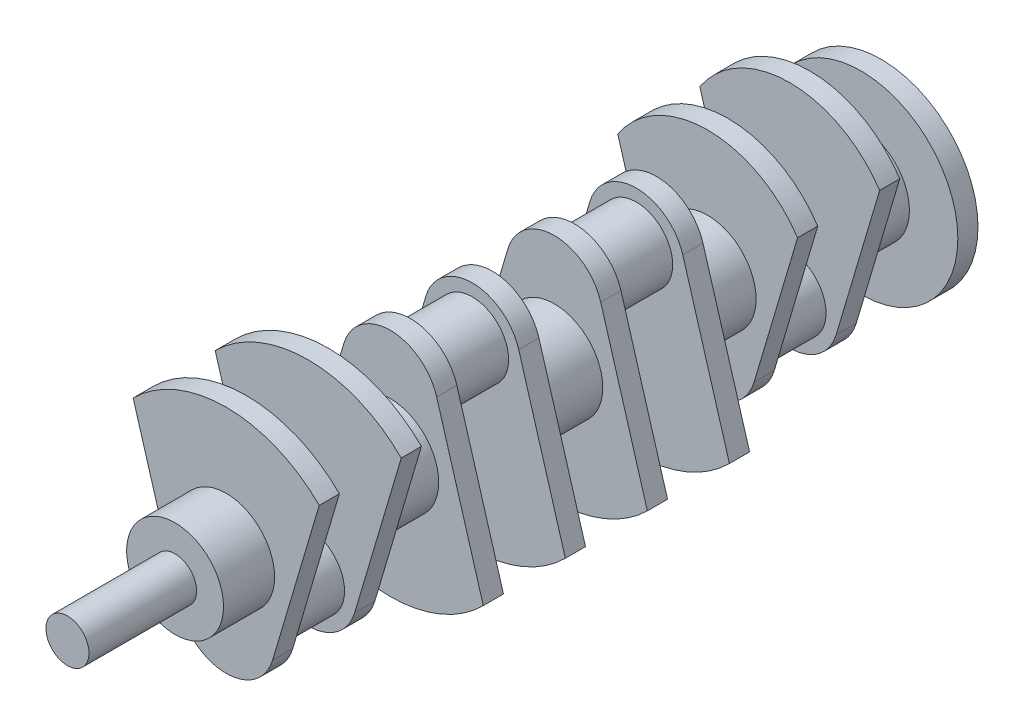
SolidWorks part; units mm, degrees
ref_plane "Plano frontal" through (0, 0, 0) normal (0, 0, 1) x (1, 0, 0)
ref_plane "Plano superior" through (0, 0, 0) normal (0, 1, 0) x (1, 0, 0)
ref_plane "Plano direito" through (0, 0, 0) normal (1, 0, 0) x (0, 0, -1)
sketch "Esboço1" plane through (0, 0, 0) normal (0, 0, 1) x (1, 0, 0)
  circle A0 centre (0, 0) radius 72
  circle A1 centre (0, 0) radius 36
  dimension "D1" = 144
  dimension "D2" = 72
extrude "Ressalto-extrusão1" add sketch "Esboço1" along normal blind 15 contours A1 | A0 A1 region at (-69.9635, 0, 0) region at (0, 0, 0)
extrude "Ressalto-extrusão2" add sketch "Esboço1<3>" along normal blind 53 contours A1 region at (0, 0, 0)
sketch "Esboço1<3>" plane through (0, 0, 0) normal (0, 0, 1) x (1, 0, 0) same geometry as "Esboço1"
sketch "Esboço2" plane through (0, 0, 53) normal (0, 0, 1) x (1, 0, 0)
  line L0 (-117.0522, 0) -> (117.0522, 0) construction
  line L1 (0, 45.2622) -> (0, -45.2622) construction
  line L2 (34.5175, -54.2246) -> (66.844, 54.9078)
  line L3 (-34.5175, -54.2246) -> (-66.844, 54.9078)
  circle A1 centre (0, -44) radius 36
  circle A2 centre (0, 0) radius 36 construction
  arc A3 (-66.844, 54.9078) -> (66.844, 54.9078) centre (0, 10.9546) cw
  point P4 (0, 0)
  point P8 (0, 0)
  circle M3 centre (0, 0) radius 36
  dimension "D1" = 72
  dimension "D2" = 44
  dimension "D4" = 80
  dimension "D3" = 33
extrude "Ressalto-extrusão3" add sketch "Esboço2" along normal blind 15 contours A3 L3 A1 L2 M3 | A1 M3 | A1 M3 | A1 M3 region at (0, 42.7995, 53) region at (0, -52.2821, 53) region at (0, 8.2821, 53) region at (0, -22, 53)
sketch "Esboço3" plane through (0, 0, 68) normal (0, 0, 1) x (1, 0, 0)
  line L0 (-140.7419, 0) -> (140.7419, 0) construction
  line L1 (0, 38.6491) -> (0, -38.6491) construction
  circle A0 centre (0, -44) radius 27
  point P4 (0, 0)
  point P8 (0, 0)
  dimension "D1" = 44
  dimension "D2" = 54
extrude "Ressalto-extrusão4" add sketch "Esboço3" along normal blind 46
sketch "Esboço4" plane through (0, 0, 114) normal (0, 0, 1) x (1, 0, 0)
  line L0 (-132.2013, 0) -> (132.2013, 0) construction
  line L1 (0, 92.3837) -> (0, -92.3837) construction
  line L2 (-34.5175, -54.2246) -> (-66.8433, 54.9054)
  line L3 (34.5175, -54.2246) -> (66.8433, 54.9054)
  circle A0 centre (0, -44) radius 36
  arc A1 (-66.8433, 54.9054) -> (66.8433, 54.9054) centre (0, 10.9512) cw
  point P4 (0, 0)
  point P8 (0, 0)
  circle M3 centre (0, -44) radius 27
  dimension "D1" = 72
  dimension "D3" = 80
  dimension "D4" = 44
  dimension "D2" = 33
  dimension "D5" = 109.13
extrude "Ressalto-extrusão5" add sketch "Esboço4" along normal blind 15 contours A1 L2 A0 L3 | A0 M3 | M3 region at (0, 34.0654, 114) region at (-5.0196, -9.3802, 114) region at (0, -44, 114)
sketch "Esboço5" plane through (0, 0, 129) normal (0, 0, 1) x (1, 0, 0)
  line L0 (-127.5752, 0) -> (127.5752, 0) construction
  line L1 (0, 51.1041) -> (0, -51.1041) construction
  circle A0 centre (0, 0) radius 36
  point P4 (0, 0)
  point P8 (0, 0)
  dimension "D1" = 72
extrude "Ressalto-extrusão6" add sketch "Esboço5" along normal blind 38
sketch "Esboço6" plane through (0, 0, 167) normal (0, 0, 1) x (1, 0, 0)
  line L0 (0, 135.2261) -> (0, -162.3966) construction
  line L1 (-34.5175, 54.2246) -> (-69.1758, -62.7797)
  line L2 (34.5175, 54.2246) -> (69.1758, -62.7797)
  circle A0 centre (0, 44) radius 36
  circle A1 centre (0, 0) radius 36 construction
  arc A2 (-69.1758, -62.7797) -> (69.1758, -62.7797) centre (0, 6.396) ccw
  circle M1 centre (0, 0) radius 36
  dimension "D1" = 72
  dimension "D2" = 44
  dimension "D3" = 33
extrude "Ressalto-extrusão7" add sketch "Esboço6" along normal blind 15 contours L0 A2 L2 A0 M1 | L0 A0 L1 A2 M1 | A0 L0 M1 | L0 A0 M1 | A0 L0 M1 | L0 A0 M1 | L0 A0 M1 | L0 A0 M1 region at (16.8783, 52.2821, 167) region at (-16.8783, 52.2821, 167) region at (11.0302, 22, 167) region at (-11.0302, 22, 167) region at (33.331, -44.1593, 167) region at (-33.331, -44.1593, 167) region at (16.8783, -8.2821, 167) region at (-16.8783, -8.2821, 167)
sketch "Esboço7" plane through (0, 0, 182) normal (0, 0, 1) x (1, 0, 0)
  line L0 (0, 141.8355) -> (0, -146.754) construction
  circle A0 centre (0, 44) radius 27
  dimension "D1" = 54
  dimension "D2" = 44
extrude "Ressalto-extrusão8" add sketch "Esboço7" along normal blind 46
sketch "Esboço8" plane through (0, 0, 228) normal (0, 0, 1) x (1, 0, 0)
  line L0 (0, 154.0633) -> (0, -174.2233) construction
  line L1 (34.5175, 54.2246) -> (69.1745, -62.7754)
  line L2 (-34.5175, 54.2246) -> (-69.1745, -62.7754)
  circle A0 centre (0, 44) radius 36
  arc A1 (-69.1745, -62.7754) -> (69.1745, -62.7754) centre (0, 7.9072) ccw
  circle M4 centre (0, 44) radius 27
  dimension "D1" = 72
  dimension "D2" = 33
  dimension "D3" = 117
extrude "Ressalto-extrusão9" add sketch "Esboço8" along normal blind 15 contours A0 L0 A1 L1 | L0 A0 L2 A1 | L0 M4 | A0 L0 M4 | L0 A0 M4 | L0 M4 region at (21.058, 72.2001, 228) region at (-0.805, 75.5, 228) region at (11.4592, 44, 228) region at (-11.4592, 44, 228) region at (29.3155, -35.2045, 228) region at (-29.3155, -35.2045, 228)
sketch "Esboço11" plane through (0, 0, 243) normal (0, 0, 1) x (1, 0, 0)
  circle A0 centre (0, 0) radius 36
  dimension "D1" = 72
extrude "Ressalto-extrusão10" add sketch "Esboço11" along normal blind 46
sketch "Esboço12" plane through (0, 0, 289) normal (0, 0, 1) x (1, 0, 0)
  line L0 (0, 133.4771) -> (0, -162.5348) construction
  line L1 (34.5175, 54.2246) -> (69.1745, -62.7754)
  line L2 (-34.5175, 54.2246) -> (-69.1745, -62.7754)
  circle A0 centre (0, 44) radius 36
  arc A1 (-69.1745, -62.7754) -> (69.1745, -62.7754) centre (0, 6.399) ccw
  circle M1 centre (0, 0) radius 36
  dimension "D1" = 72
  dimension "D2" = 44
  dimension "D3" = 33
  dimension "D4" = 117
extrude "Ressalto-extrusão11" add sketch "Esboço12" along normal blind 15 contours L0 A1 L1 A0 M1 | L0 A0 L2 A1 M1 | L0 A0 M1 | L0 A0 M1 | L0 A0 M1 | L0 A0 M1 | A0 L0 M1 | A0 L0 M1 region at (16.8783, 52.2821, 289) region at (-16.8783, 52.2821, 289) region at (11.0302, 22, 289) region at (-11.0302, 22, 289) region at (33.3308, -44.1564, 289) region at (-33.3308, -44.1564, 289) region at (16.8783, -8.2821, 289) region at (-16.8783, -8.2821, 289)
sketch "Esboço13" plane through (0, 0, 304) normal (0, 0, 1) x (1, 0, 0)
  line L0 (0, 139.499) -> (0, -151.7865) construction
  circle A0 centre (0, 44) radius 27
  dimension "D1" = 54
  dimension "D2" = 44
extrude "Ressalto-extrusão12" add sketch "Esboço13" along normal blind 46
sketch "Esboço15" plane through (0, 0, 350) normal (0, 0, 1) x (1, 0, 0)
  line L0 (0, 127.6901) -> (0, -152.4425) construction
  line L1 (-34.5175, 54.2246) -> (-69.1745, -62.7754)
  line L2 (34.5175, 54.2246) -> (69.1745, -62.7754)
  circle A2 centre (0, 44) radius 36
  arc A3 (-69.1745, -62.7754) -> (69.1745, -62.7754) centre (0, 6.0031) ccw
  circle M1 centre (0, 44) radius 27
  dimension "D1" = 72
  dimension "D2" = 44
  dimension "D3" = 33
  dimension "D4" = 117
extrude "Ressalto-extrusão13" add sketch "Esboço15" along normal blind 15 contours L0 A2 L1 A3 | A2 L0 A3 L2 | L0 M1 | L0 M1 | A2 L0 M1 | A2 region at (21.058, 72.2001, 350) region at (11.4592, 44, 350) region at (-11.4592, 44, 350) region at (29.3077, -35.4366, 350) region at (-29.3077, -35.4366, 350)
sketch "Esboço16" plane through (0, 0, 365) normal (0, 0, 1) x (1, 0, 0)
  line L0 (0, 141.498) -> (0, -185.4139) construction
  circle A0 centre (0, 0) radius 36
  dimension "D1" = 72
extrude "Ressalto-extrusão14" add sketch "Esboço16" along normal blind 46
sketch "Esboço18" plane through (0, 0, 411) normal (0, 0, 1) x (1, 0, 0)
  line L0 (0, 175.3672) -> (0, -173.498) construction
  line L1 (-34.5175, -54.2246) -> (-69.1745, 62.7754)
  line L2 (34.5175, -54.2246) -> (69.1745, 62.7754)
  circle A0 centre (0, -44) radius 36
  arc A1 (-69.1745, 62.7754) -> (69.1745, 62.7754) centre (0, -6.399) cw
  circle M2 centre (0, 0) radius 36
  dimension "D1" = 72
  dimension "D2" = 44
  dimension "D3" = 33
  dimension "D4" = 117
extrude "Ressalto-extrusão15" add sketch "Esboço18" along normal blind 15 contours L0 A1 L1 A0 M2 | A1 L0 A0 L2 M2 | L0 A0 M2 | L0 A0 M2 | L0 A0 M2 | L0 A0 M2 | A0 L0 M2 | L0 A0 M2 region at (33.3308, 44.1564, 411) region at (-33.3308, 44.1564, 411) region at (16.8783, 8.2821, 411) region at (-16.8783, 8.2821, 411) region at (11.0302, -22, 411) region at (-11.0302, -22, 411) region at (-16.8783, -52.2821, 411) region at (16.8783, -52.2821, 411)
sketch "Esboço19" plane through (0, 0, 426) normal (0, 0, 1) x (1, 0, 0)
  line L0 (0, 126.7736) -> (0, -179.6794) construction
  circle A1 centre (0, -44) radius 27
  dimension "D1" = 54
  dimension "D2" = 44
extrude "Ressalto-extrusão16" add sketch "Esboço19" along normal blind 46
sketch "Esboço20" plane through (0, 0, 472) normal (0, 0, 1) x (1, 0, 0)
  line L0 (0, 123.6748) -> (0, -127.0819) construction
  line L1 (-34.5175, -54.2246) -> (-69.1745, 62.7754)
  line L2 (34.5175, -54.2246) -> (69.1745, 62.7754)
  circle A0 centre (0, -44) radius 36
  arc A1 (-69.1745, 62.7754) -> (69.1745, 62.7754) centre (0, -6.399) cw
  circle M1 centre (0, -44) radius 27
  dimension "D1" = 72
  dimension "D2" = 33
  dimension "D3" = 117
extrude "Ressalto-extrusão17" add sketch "Esboço20" along normal blind 15 contours A1 L0 A0 L2 | L0 A1 L1 A0 | L0 A0 M1 | A0 L0 M1 | L0 M1 | L0 M1 region at (29.3093, 35.3876, 472) region at (-29.3093, 35.3876, 472) region at (24.8866, -19.1134, 472) region at (-0.805, -12.5, 472) region at (11.4592, -44, 472) region at (-11.4592, -44, 472)
sketch "Esboço21" plane through (0, 0, 487) normal (0, 0, 1) x (1, 0, 0)
  line L0 (0, 122.2005) -> (0, -150.7491) construction
  circle A0 centre (0, 0) radius 36
  dimension "D1" = 72
extrude "Ressalto-extrusão18" add sketch "Esboço21" along normal blind 38
sketch "Esboço22" plane through (0, 0, 525) normal (0, 0, 1) x (1, 0, 0)
  circle A0 centre (0, 0) radius 16
  dimension "D1" = 32
extrude "Ressalto-extrusão19" add sketch "Esboço22" along normal blind 80
